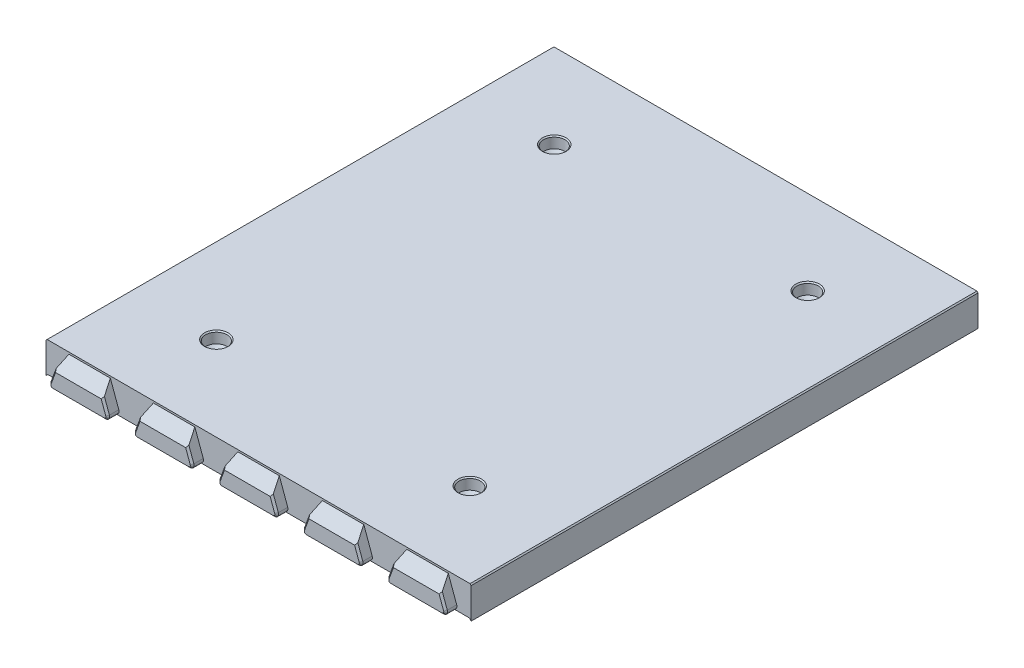
SolidWorks part; units mm, degrees
ref_plane "Front Plane" through (0, 0, 0) normal (0, 0, 1) x (1, 0, 0)
ref_plane "Top Plane" through (0, 0, 0) normal (0, 1, 0) x (1, 0, 0)
ref_plane "Right Plane" through (0, 0, 0) normal (1, 0, 0) x (0, 0, -1)
sketch "Sketch1" plane through (0, 0, 0) normal (0, 0, 1) x (1, 0, 0)
  line L0 (0, 0) -> (0, 8) construction
  line L1 (-56.625, 0) -> (0, 0) construction
  line L2 (-56.625, 0) -> (-56.625, 8)
  line L3 (-56.625, 8) -> (56.625, 8)
  line L5 (-56.625, 0) -> (-54.625, 0)
  line L6 (-54.625, 0) -> (-54.625, 6)
  line L7 (-54.625, 6) -> (54.625, 6)
  line L9 (54.625, 0) -> (54.625, 6)
  line L10 (56.625, 0) -> (54.625, 0)
  line L11 (56.625, 0) -> (56.625, 8)
  point P8 (0, 6)
  dimension "D2" = 6
  dimension "D1" = 56.625
  dimension "D3" = 2
  dimension "D4" = 2
extrude "Boss-Extrude1" add sketch "Sketch1" against normal blind 67.5
sketch "Sketch7" plane through (0, 0, 0) normal (0, 0, 1) x (1, 0, 0)
  line L2 (-54.625, 0) -> (54.625, 0)
  line L13 (-54.625, 0) -> (-54.625, 6)
  line L15 (-54.625, 6) -> (54.625, 6)
  line L16 (54.625, 0) -> (54.625, 6)
  line M3 (-54.625, 0) -> (-54.625, 6)
  line M4 (-54.625, 6) -> (54.625, 6)
  line M5 (54.625, 6) -> (54.625, 0)
extrude "Boss-Extrude7" add sketch "Sketch7" against normal blind 1 contours M4 M3 | M5 region at (0, 3, 0)
sketch "Sketch2" plane through (0, 0, 0) normal (0, 0, 1) x (1, 0, 0)
  line L14 (39.6618, 8) -> (36.75, 0)
  line L15 (56.625, 8) -> (-56.625, 8) construction
  line L16 (-56.625, 0) -> (56.625, 0) construction
  line L17 (36.75, 0) -> (53.25, 0)
  line L18 (39.6618, 8) -> (50.3382, 8)
  line L19 (-56.625, 0) -> (56.625, 0) construction
  line L21 (50.3382, 8) -> (53.25, 0)
  line L24 (33.75, 0) -> (33.75, 8) construction
  line L27 (17.1618, 8) -> (14.25, 0)
  line L28 (17.1618, 8) -> (27.8382, 8)
  line L29 (14.25, 0) -> (30.75, 0)
  line L30 (27.8382, 8) -> (30.75, 0)
  line L31 (-5.3382, 8) -> (-8.25, 0)
  line L32 (-5.3382, 8) -> (5.3382, 8)
  line L33 (-8.25, 0) -> (8.25, 0)
  line L34 (5.3382, 8) -> (8.25, 0)
  line L35 (-27.8382, 8) -> (-30.75, 0)
  line L36 (-27.8382, 8) -> (-17.1618, 8)
  line L37 (-30.75, 0) -> (-14.25, 0)
  line L38 (-17.1618, 8) -> (-14.25, 0)
  line L39 (39.6618, 8) -> (17.1618, 8) construction
  line L40 (56.25, 8) -> (56.25, 0) construction
  line L41 (56.625, 0) -> (56.625, 8) construction
  line L42 (-56.25, 8) -> (-56.25, 0) construction
  line L43 (-56.625, 8) -> (-56.625, 0) construction
  line L44 (-50.3382, 8) -> (-53.25, 0)
  line L45 (-50.3382, 8) -> (-39.6618, 8)
  line L46 (-53.25, 0) -> (-36.75, 0)
  line L47 (-39.6618, 8) -> (-36.75, 0)
  point P22 (45, 8)
  point P23 (22.5, 8)
  dimension "D1" = 70
  dimension "D2" = 0.375
  dimension "D3" = 3
  dimension "D4" = 3
  dimension "D5" = 70
  dimension "D7" = 22.5
  dimension "D8" = 22.5
  dimension "D9" = 0.375
  dimension "D10" = 25.5
  dimension "D11" = 8
  dimension "D6" = 5
extrude "Boss-Extrude4" add sketch "Sketch2" along normal blind 3
sketch "Sketch8" plane through (0, 0, 0) normal (0, -1, 0) x (1, 0, 0)
  line L0 (-56.625, -22.5) -> (56.625, -22.5) construction
  line L2 (56.625, -67.5) -> (56.625, 0) construction
  line L3 (-56.625, 0) -> (-53.25, 0) construction
  line L4 (-55.25, -24.9559) -> (-55.25, -20.0441)
  line L5 (-55.25, -20.0441) -> (-51.25, -21.5)
  line L6 (-51.25, -21.5) -> (-51.25, -23.5)
  line L7 (-55.25, -67.5) -> (-55.25, -65.0441)
  line L8 (-55.25, -65.0441) -> (-51.25, -66.5)
  line L9 (-51.25, -66.5) -> (-51.25, -67.5)
  line L10 (-54.625, -67.5) -> (54.625, -67.5) construction
  line L11 (-51.25, -67.5) -> (-55.25, -67.5)
  line L12 (-55.25, -24.9559) -> (-51.25, -23.5)
  line L13 (0, -67.5) -> (0, 0) construction
  line L23 (-56.625, -67.5) -> (-56.625, 0) construction
  line L24 (55.25, -24.9559) -> (51.25, -23.5)
  line L25 (51.25, -21.5) -> (51.25, -23.5)
  line L26 (55.25, -20.0441) -> (51.25, -21.5)
  line L27 (55.25, -24.9559) -> (55.25, -20.0441)
  line L28 (-56.625, -67.5) -> (-54.625, -67.5) construction
  line L29 (51.25, -67.5) -> (55.25, -67.5)
  line L30 (51.25, -66.5) -> (51.25, -67.5)
  line L31 (55.25, -65.0441) -> (51.25, -66.5)
  line L32 (55.25, -67.5) -> (55.25, -65.0441)
  point P19 (-51.25, -22.5)
  point P32 (51.25, -22.5)
  dimension "D1" = 22.5
  dimension "D2" = 1.375
  dimension "D3" = 70
  dimension "D4" = 4
  dimension "D6" = 4
  dimension "D7" = 70
  dimension "D8" = 1
  dimension "D9" = 1
  dimension "D10" = 102.5
  dimension "D11" = 110.5
extrude "Boss-Extrude8" add sketch "Sketch8" against normal up to next and the other way blind 2
chamfer "Chamfer4" distance 0.5 angle 45 14 edges at (-51.25, -2, -67) (-53.25, -2, -65.7721) (-55.25, -2, -66.2721) (-53.25, -2, -24.2279) (-51.25, -2, -22.5) (-53.25, -2, -20.7721) (51.25, -2, -22.5) (53.25, -2, -24.2279) (53.25, -2, -20.7721) (55.25, -2, -22.5) (51.25, -2, -67) (55.25, -2, -66.2721) (53.25, -2, -65.7721) (-55.25, -2, -22.5)
fillet "Fillet4" radius 1 10 edges at (53.25, 0, 1.5) (36.75, 0, 1.5) (30.75, 0, 1.5) (14.25, 0, 1.5) (8.25, 0, 1.5) (-8.25, 0, 1.5) (-14.25, 0, 1.5) (-30.75, 0, 1.5) (-36.75, 0, 1.5) (-53.25, 0, 1.5)
chamfer "Chamfer6" distance 0.5 angle 45 25 edges at (38.4501, 4.671, 3) (51.5499, 4.671, 3) (45, 0, 3) (-29.0499, 4.671, 3) (-22.5, 0, 3) (-15.9501, 4.671, 3) (-6.5499, 4.671, 3) (0, 0, 3) (6.5499, 4.671, 3) (15.9501, 4.671, 3) (29.0499, 4.671, 3) (22.5, 0, 3) (-38.4501, 4.671, 3) (-45, 0, 3) (-51.5499, 4.671, 3) (-37.359, 0.4264, 3) (-52.641, 0.4264, 3) (-30.141, 0.4264, 3) (-14.859, 0.4264, 3) (-7.641, 0.4264, 3) (7.641, 0.4264, 3) (14.859, 0.4264, 3) (30.141, 0.4264, 3) (37.359, 0.4264, 3) (52.641, 0.4264, 3)
fillet "Fillet2" radius 2 23 edges at (0, 6, -1) (-54.625, 3, -65.2716) (-52.9375, 6, -65.8858) (-51.25, 6, -67) (-54.625, 3, -1) (-52.9375, 6, -20.8858) (-54.625, 3, -20.2716) (-54.625, 6, -45) (-51.25, 6, -22.5) (-52.9375, 6, -24.1142) (-54.625, 3, -24.7284) (54.625, 6, -10.6358) (54.625, 3, -1) (-54.625, 6, -10.6358) (54.625, 3, -24.7284) (54.625, 3, -20.2716) (54.625, 3, -65.2716) (51.25, 6, -67) (52.9375, 6, -65.8858) (52.9375, 6, -20.8858) (51.25, 6, -22.5) (54.625, 6, -45) (52.9375, 6, -24.1142)
mirror "Mirror2" about plane through (0, 0, -67.5) normal (0, 0, 1) of "Fillet4", "Boss-Extrude1", "Boss-Extrude7", "Boss-Extrude4", "Boss-Extrude8", "Chamfer4", "Fillet2", "Chamfer6"
sketch "Sketch9" plane through (0, 0, 0) normal (0, 1, 0) x (1, 0, 0)
  line L16 (-33.75, 22.5) -> (33.75, 22.5) construction
  line L17 (-56.625, 67.5) -> (56.625, 67.5) construction
  line L18 (-56.625, 70.4563) -> (-56.625, 64.5437) construction
  line L20 (56.625, 135) -> (56.625, 0) construction
  line L24 (0, 22.5) -> (0, 67.5) construction
  circle A0 centre (-33.75, 22.5) radius 5
  circle A1 centre (33.75, 22.5) radius 5
  circle A4 centre (33.75, 112.5) radius 5
  circle A5 centre (-33.75, 112.5) radius 5
  point P23 (0, 67.5)
  point P24 (0, 67.5)
  dimension "D3" = 10
  dimension "D1" = 45
  dimension "D2" = 67.5
extrude "Boss-Extrude9" add sketch "Sketch9" along normal up to next
fillet "Fillet3" radius 3 4 edges at (33.75, 6, -27.5) (-33.75, 6, -27.5) (33.75, 6, -117.5) (-33.75, 6, -117.5)
sketch "Sketch10" plane through (0, 0, 0) normal (0, 1, 0) x (1, 0, 0)
  circle A0 centre (-33.75, 112.5) radius 1.85
  circle A1 centre (-33.75, 22.5) radius 1.85
  circle A2 centre (33.75, 22.5) radius 1.85
  circle A3 centre (33.75, 112.5) radius 1.85
  circle A4 centre (-33.75, 22.5) radius 5 construction
  circle A5 centre (33.75, 22.5) radius 5 construction
  circle A8 centre (-33.75, 22.5) radius 5 construction
  circle A9 centre (33.75, 22.5) radius 5 construction
  dimension "D1" = 3.7
extrude "Cut-Extrude2" cut sketch "Sketch10" along normal through all
sketch "Sketch11" plane through (0, 8, 0) normal (0, 1, 0) x (1, 0, 0)
  circle A0 centre (-33.75, 112.5) radius 2.85
  circle A1 centre (33.75, 112.5) radius 2.85
  circle A2 centre (33.75, 22.5) radius 2.85
  circle A3 centre (-33.75, 22.5) radius 2.85
  dimension "D1" = 5.7
extrude "Cut-Extrude3" cut sketch "Sketch11" against normal blind 3
chamfer "Chamfer7" distance 1 angle 45 4 edges at (33.75, 5, -110.65) (-33.75, 5, -110.65) (33.75, 5, -20.65) (-33.75, 5, -20.65)
sketch "Sketch12" plane through (0, 0, 0) normal (1, 0, 0) x (0, 0, -1)
  line L0 (0, 7.5) -> (-3, 4.5)
  line L1 (-3, 1.171) -> (-3, 8) construction
  line L2 (-3, 4.5) -> (-3, 7.5)
  line L3 (-3, 7.5) -> (0, 7.5) construction
  line L4 (67.5, 8) -> (67.5, 0) construction
  line L5 (135, 8) -> (0, 8) construction
  line L6 (135, 0) -> (0, 0) construction
  line L8 (138, 4.5) -> (138, 7.5)
  line L9 (135, 7.5) -> (138, 4.5)
  line L10 (0, 0) -> (0, 8) construction
  line L11 (-3, 8) -> (-2.5, 8) construction
  line L12 (-3, 7.5) -> (-3, 8)
  line L13 (-3, 8) -> (0, 8)
  line L14 (0, 8) -> (0, 7.5)
  line L15 (138, 7.5) -> (135, 7.5) construction
  line L16 (135, 8) -> (135, 7.5)
  line L17 (138, 8) -> (135, 8)
  line L18 (138, 7.5) -> (138, 8)
  dimension "D1" = 45
  dimension "D2" = 3
  dimension "D3" = 0.5
extrude "Cut-Extrude4" cut sketch "Sketch12" against normal through all both and the other way through all
sketch "Sketch13" plane through (0, 0, -135) normal (0, 0, -1) x (-1, 0, 0)
  line L0 (-56.125, 0) -> (-56.625, -0.5)
  line L1 (-51.8219, 0) -> (-56.625, 0) construction
  line L2 (-56.625, -0.5) -> (-56.625, 0)
  line L3 (-56.625, 0) -> (-56.125, 0)
  line L4 (0, 0) -> (0, 8) construction
  line L5 (-56.625, 8) -> (56.625, 8) construction
  line L6 (56.625, 0) -> (56.125, 0)
  line L7 (56.625, -0.5) -> (56.625, 0)
  line L8 (56.125, 0) -> (56.625, -0.5)
  dimension "D1" = 0.5
  dimension "D2" = 0.5
extrude "Boss-Extrude10" add sketch "Sketch13" against normal up to surface (135 mm away) up to face at (0, 2.9992, 0)
chamfer "Chamfer8" distance 0.3 angle 45 6 edges at (-56.625, 8, -67.5) (56.625, 8, -67.5) (-33.75, 8, -109.65) (33.75, 8, -109.65) (-33.75, 8, -19.65) (33.75, 8, -19.65)
